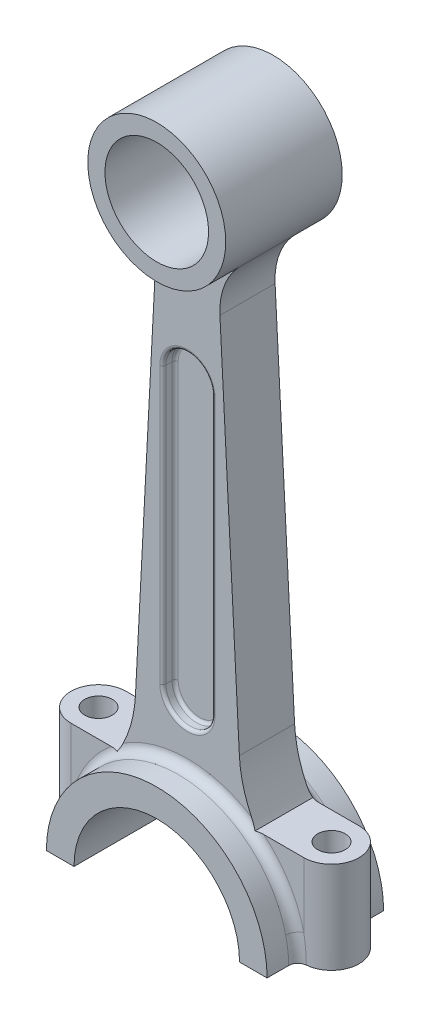
SolidWorks part; units mm, degrees
ref_plane "Front Plane" through (0, 0, 0) normal (0, 0, 1) x (1, 0, 0)
ref_plane "Top Plane" through (0, 0, 0) normal (0, 1, 0) x (1, 0, 0)
ref_plane "Right Plane" through (0, 0, 0) normal (1, 0, 0) x (0, 0, -1)
sketch "Sketch1" plane through (0, 0, 0) normal (0, 0, 1) x (1, 0, 0)
  line L0 (0, 0) -> (0, -201.2) construction
  line L1 (-10, -20.1556) -> (-17.8497, -169.9368)
  line L2 (10, -20.1556) -> (17.8497, -169.9368)
  line L3 (-36, -201.2) -> (-27, -201.2)
  line L4 (27, -201.2) -> (36, -201.2)
  circle A0 centre (0, 0) radius 22.5
  circle A1 centre (0, 0) radius 16.9
  arc A2 (36, -201.2) -> (-36, -201.2) centre (0, -201.2) ccw
  arc A3 (27, -201.2) -> (-27, -201.2) centre (0, -201.2) ccw
  dimension "D1" = 45
  dimension "D2" = 33.8
  dimension "D3" = 54
  dimension "D4" = 72
  dimension "D5" = 201.2
  dimension "D6" = 20
  dimension "D7" = 6
extrude "Boss-Extrude2" add sketch "Sketch1" along normal mid plane 38 contours A1 A0 | A2 A3 | L4 A2 L3 A3 region at (-11.5231, 18.5805, 0) region at (0, -166.005, 0)
extrude "Boss-Extrude3" add sketch "Sketch1<4>" along normal mid plane 18 contours L0 A0 L1 A2 | A0 L0 A2 L2 region at (7.1843, -100.8455, 0) region at (-7.1843, -100.8455, 0)
sketch "Sketch1<4>" plane through (0, 0, 0) normal (0, 0, 1) x (1, 0, 0) same geometry as "Sketch1"
sketch "Sketch2" plane through (0, 0, 9) normal (0, 0, 1) x (1, 0, 0)
  line L0 (0, 0) -> (0, -201.2) construction
  line L1 (0, -145.6) -> (0, -55.6) construction
  line L2 (-8, -145.6) -> (-8, -55.6)
  line L3 (8, -145.6) -> (8, -55.6)
  arc A0 (-8, -145.6) -> (8, -145.6) centre (0, -145.6) ccw
  arc A1 (8, -55.6) -> (-8, -55.6) centre (0, -55.6) ccw
  point P6 (0, -100.6)
  dimension "D2" = 8
  dimension "D1" = 90
extrude "Cut-Extrude1" cut sketch "Sketch2" against normal blind 4
mirror "Mirror1" about plane through (0, 0, 0) normal (0, 0, 1) of "Cut-Extrude1"
fillet "Fillet2" radius 40 2 edges at (-17.8497, -169.9368, 0) (17.8497, -169.9368, 0)
fillet "Fillet3" radius 22.5 2 edges at (-10, -20.1556, 0) (10, -20.1556, 0)
fillet "Fillet1" radius 1 16 edges at (0, -47.6, -5) (8, -100.6, -5) (0, -153.6, -5) (0, -47.6, -9) (8, -100.6, -9) (0, -153.6, -9) (0, -47.6, 9) (8, -100.6, 9) (0, -153.6, 9) (-8, -100.6, 5) (0, -47.6, 5) (8, -100.6, 5) (0, -153.6, 5) (-8, -100.6, -5) (-8, -100.6, -9) (-8, -100.6, 9)
ref_plane "Plane1" through (0, -171.2, 0) normal (0, -1, 0) x (-1, 0, 0)
sketch "Sketch3" plane through (0, -171.2, 0) normal (0, -1, 0) x (-1, 0, 0)
  line L0 (38, 0) -> (-38, 0) construction
  line L1 (38, -9) -> (-38, -9)
  line L2 (38, 9) -> (-38, 9)
  arc A0 (38, -9) -> (38, 9) centre (38, 0) ccw
  arc A1 (-38, 9) -> (-38, -9) centre (-38, 0) ccw
  point P2 (0, 0)
  dimension "D2" = 9
  dimension "D1" = 76
extrude "Boss-Extrude4" add sketch "Sketch3" along normal up to surface (30 mm away) up to face at (-31.5, -201.2, 0)
sketch "Sketch5" plane through (0, 0, -9) normal (0, 0, -1) x (-1, 0, 0)
  arc A0 (27, -201.2) -> (-27, -201.2) centre (0, -201.2) ccw construction
  arc A1 (27, -201.2) -> (-27, -201.2) centre (0, -201.2) ccw
extrude "Cut-Extrude2" cut sketch "Sketch5" against normal through all and the other way through all
sketch "Sketch6" plane through (0, -171.2, 0) normal (0, 1, 0) x (1, 0, 0)
  circle A0 centre (38, 0) radius 4.5
  circle A1 centre (-38, 0) radius 4.5
  dimension "D1" = 9
  dimension "D2" = 9
extrude "Cut-Extrude3" cut sketch "Sketch6" against normal through all
fillet "Fillet4" radius 3 2 edges at (0, -165.2, 9) (0, -165.2, -9)
